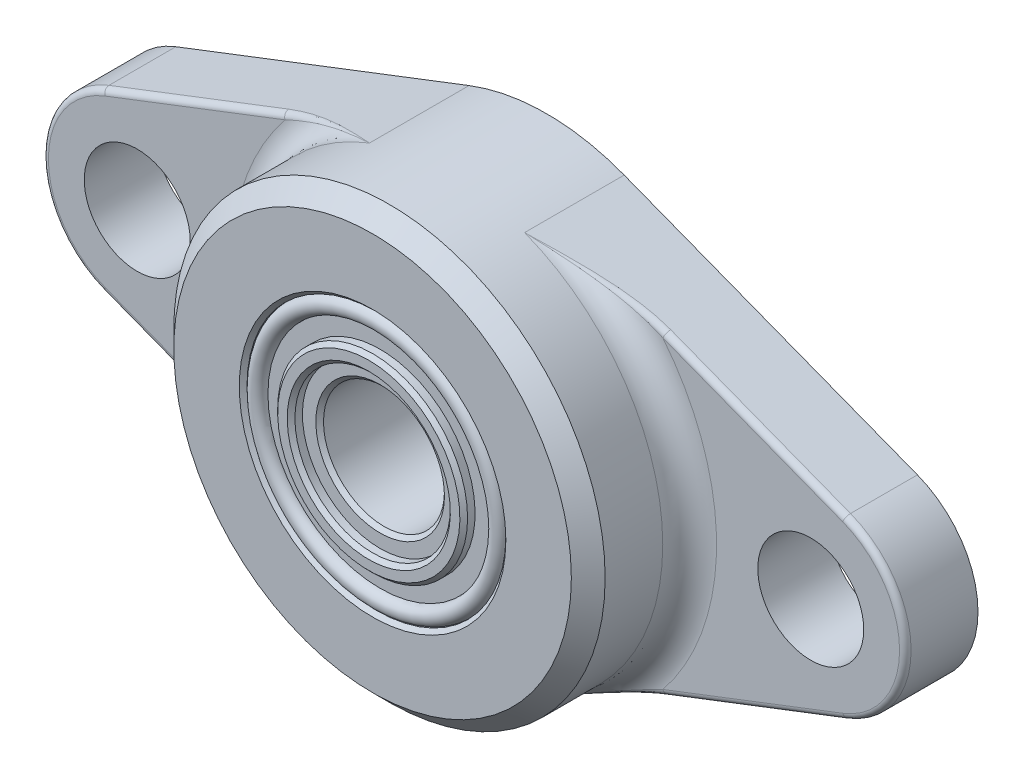
SolidWorks part; units mm, degrees
ref_plane "Front Plane" through (0, 0, 0) normal (0, 0, 1) x (1, 0, 0)
ref_plane "Top Plane" through (0, 0, 0) normal (0, 1, 0) x (1, 0, 0)
ref_plane "Right Plane" through (0, 0, 0) normal (1, 0, 0) x (0, 0, -1)
sketch "Sketch1" plane through (0, 0, 0) normal (0, 0, 1) x (1, 0, 0)
  line L0 (-22.25, 0) -> (22.25, 0) construction
  line L1 (0, 14.25) -> (0, -14.25) construction
  line L2 (-24.4972, 5.832) -> (-5.1236, 13.297)
  line L3 (5.1236, 13.297) -> (24.4972, 5.832)
  line L4 (24.4972, -5.832) -> (5.1236, -13.297)
  line L5 (-24.4972, -5.832) -> (-5.1236, -13.297)
  line L6 (-28.5, 0) -> (28.5, 0) construction
  line L7 (2.8249, 2.8249) -> (10.0763, 10.0763) construction
  circle A0 centre (-22.25, 0) radius 3.5
  circle A1 centre (22.25, 0) radius 3.5
  circle A2 centre (0, 0) radius 14.25
  arc A3 (-24.4972, 5.832) -> (-24.4972, -5.832) centre (-22.25, 0) ccw
  arc A4 (24.4972, -5.832) -> (24.4972, 5.832) centre (22.25, 0) ccw
  circle A5 centre (0, 0) radius 3.995
  circle A6 centre (0, 0) radius 8.5528 construction
  point P23 (6.0477, 6.0477)
  point P24 (0, 8.5528)
  point P25 (0, 3.995)
  dimension "Mounting Hole" = 7
  dimension "ID" = 7.99
  dimension "D4" = 17.1056
  dimension "Mounting Center" = 44.5
  dimension "Height" = 28.5
  dimension "Length" = 57
  dimension "D2" = 45
  dimension "D3" = 10.255
  dimension "D1" = 4.5578
sketch "Sketch2" plane through (0, 0, 0) normal (1, 0, 0) x (0, 0, -1)
  line L0 (5.75, 0) -> (-5.75, 0) construction
  point P2 (0.95, 0)
  point P4 (5.75, 0)
  dimension "Width" = 11.5
  dimension "flange thickness" = 4.8
  dimension "Bearing Width" = 11.5
sketch "Sketch3" plane through (0, 0, 0) normal (0, 0, 1) x (1, 0, 0)
  line L0 (-24.4972, 5.832) -> (-5.1236, 13.297) construction
  line L1 (5.1236, 13.297) -> (24.4972, 5.832) construction
  line L2 (24.4972, -5.832) -> (5.1236, -13.297) construction
  line L3 (-24.4972, -5.832) -> (-5.1236, -13.297) construction
  line L4 (-24.4972, 5.832) -> (-5.1236, 13.297)
  line L5 (5.1236, 13.297) -> (24.4972, 5.832)
  line L6 (24.4972, -5.832) -> (5.1236, -13.297)
  line L7 (-24.4972, -5.832) -> (-5.1236, -13.297)
  arc A0 (-24.4972, 5.832) -> (-24.4972, -5.832) centre (-22.25, 0) ccw construction
  circle A1 centre (-22.25, 0) radius 3.5 construction
  circle A2 centre (0, 0) radius 14.25 construction
  circle A3 centre (22.25, 0) radius 3.5 construction
  arc A4 (24.4972, -5.832) -> (24.4972, 5.832) centre (22.25, 0) ccw construction
  arc A5 (-24.4972, 5.832) -> (-24.4972, -5.832) centre (-22.25, 0) ccw
  circle A6 centre (-22.25, 0) radius 3.5
  arc A7 (-5.1236, -13.297) -> (5.1236, -13.297) centre (0, 0) ccw
  circle A8 centre (22.25, 0) radius 3.5
  arc A9 (24.4972, -5.832) -> (24.4972, 5.832) centre (22.25, 0) ccw
  circle A10 centre (0, 0) radius 8.5528 construction
  circle A11 centre (0, 0) radius 8.5528
  arc A12 (5.1236, 13.297) -> (-5.1236, 13.297) centre (0, 0) ccw
extrude "Boss-Extrude1" add sketch "Sketch3" along normal up to vertex (-0.95 mm away) from vertex at -5.75 starting at point (0, 0, -5.75)
sketch "Sketch4" plane through (0, 0, -0.95) normal (0, 0, 1) x (1, 0, 0)
  circle A0 centre (0, 0) radius 14.25 construction
  circle A1 centre (0, 0) radius 8.5528 construction
  circle A2 centre (0, 0) radius 14.25
  circle A3 centre (0, 0) radius 8.5528
extrude "Boss-Extrude2" add sketch "Sketch4" along normal up to vertex
chamfer "Chamfer1" distance 0.254 angle 45 2 edges at (8.5528, 0, 5.75) (8.5528, 0, -5.75)
fillet "Fillet1" radius 1.778 2 edges
fillet "Fillet2" radius 0.381 10 edges at (8.6519, 11.9375, -0.401) (28.5, 0, -0.95) (-8.6519, 11.9375, -0.401) (-28.5, 0, -0.95) (-8.6519, -11.9375, -0.401) (8.6519, -11.9375, -0.401)
chamfer "Chamfer2" distance 1.1167 angle 45 1 edges at (14.25, 0, 5.75)
sketch "Sketch5" plane through (0, 0, 0) normal (1, 0, 0) x (0, 0, -1)
  line L0 (-5.75, 3.995) -> (5.75, 3.995)
  line L1 (-5.75, 3.995) -> (-5.75, 8.5528)
  line L2 (-5.75, 8.5528) -> (5.75, 8.5528)
  line L3 (5.75, 8.5528) -> (5.75, 3.995)
  line L4 (-5.75, 0) -> (5.75, 0) construction
  dimension "D1" = 11.5
sketch "Sketch6" plane through (0, 0, 0) normal (1, 0, 0) x (0, 0, -1)
  line L0 (-5.75, 0) -> (5.75, 0) construction
  line L1 (5.75, -8.8068) -> (5.75, 8.8068) construction
  line L2 (-5.25, 3.995) -> (3.75, 3.995)
  line L3 (3.75, 3.995) -> (3.75, 5.1344)
  line L4 (3.75, 5.1344) -> (4.5, 5.1344)
  line L5 (4.5, 5.1344) -> (4.5, 6.2739)
  line L10 (4.5, 6.2739) -> (3, 6.2739)
  line L11 (3, 6.2739) -> (3, 7.4133)
  line L12 (3, 7.4133) -> (5.75, 7.4133)
  line L13 (5.75, 7.4133) -> (5.75, 8.5528)
  line L14 (5.75, 8.5528) -> (-5.25, 8.5528)
  line L18 (-5.25, 7.4133) -> (-5.25, 6.2739)
  line L19 (-5.25, 6.2739) -> (-6, 6.2739)
  line L20 (-6, 6.2739) -> (-6, 5.1344)
  line L21 (-6, 5.1344) -> (-5.25, 5.1344)
  line L22 (-5.25, 5.1344) -> (-5.25, 3.995)
  line L24 (5.75, 5.832) -> (5.75, 13.297) construction
  arc A0 (-5.25, 8.5528) -> (-5.25, 7.4133) centre (-5.25, 7.9831) ccw
  point P5 (0, 0)
  point P30 (3.75, 6.2739)
  dimension "D1" = 0.5
  dimension "D3" = 0.25
  dimension "D7" = 1.25
  dimension "D8" = 1.5
revolve "Revolve1" add sketch "Sketch6" angle 360 about L0
chamfer "Chamfer3" distance 0.254 angle 45 3 edges at (0, -5.1344, 6) (0, -3.995, 5.25) (0, -6.2739, 6)
chamfer "Chamfer4" distance 0.254 angle 45 3 edges at (0, -3.995, -3.75) (0, -5.1344, -4.5) (0, -6.2739, -4.5)
equation "\"D1@Chamfer2\"=(\"Width@Sketch2\"-\"flange thickness@Sketch2\")/6"
equation "\"D1@Sketch1\"=\"D3@Sketch1\"/2.25"
equation "\"D1@Sketch5\"=\"Bearing Width@Sketch2\""
